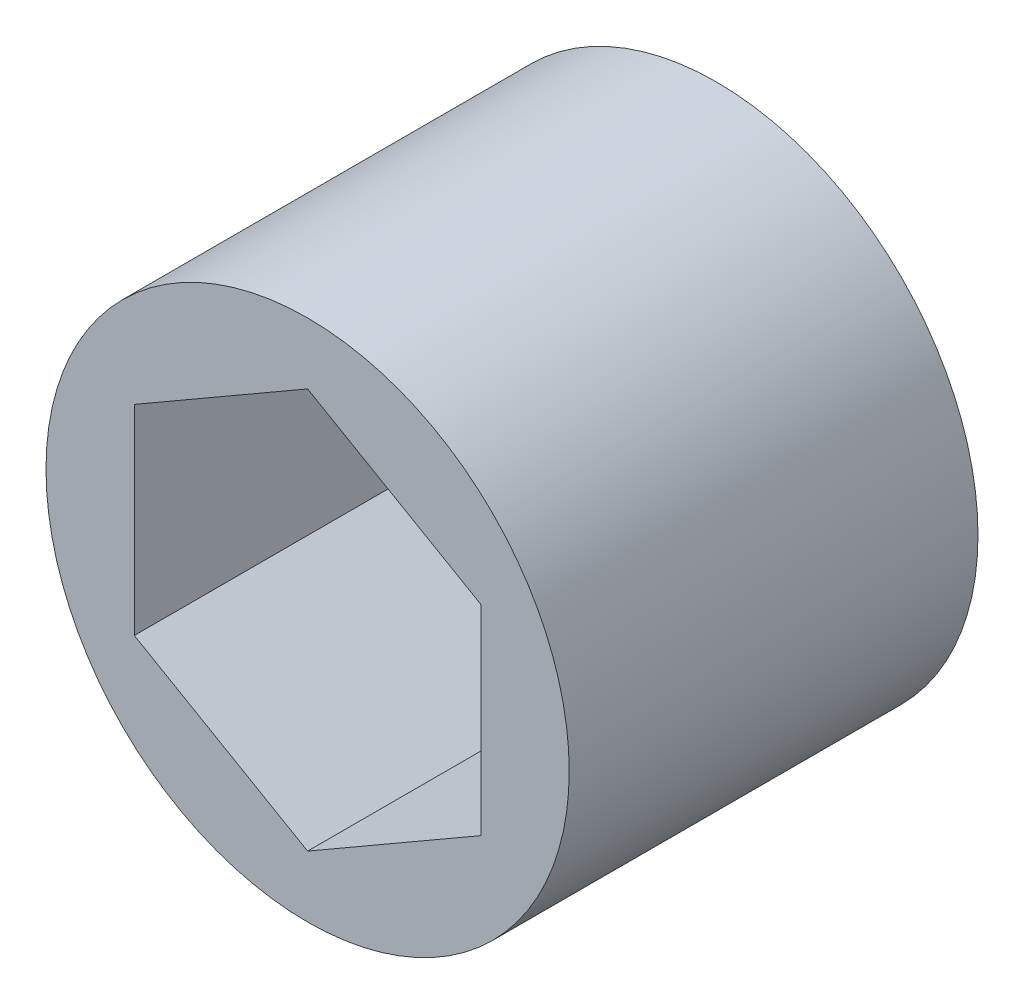
SolidWorks part; units mm, degrees
material "Nylon 101"
ref_plane "Front Plane" through (0, 0, 0) normal (0, 0, 1) x (1, 0, 0)
ref_plane "Top Plane" through (0, 0, 0) normal (0, 1, 0) x (1, 0, 0)
ref_plane "Right Plane" through (0, 0, 0) normal (1, 0, 0) x (0, 0, -1)
sketch "Sketch3" plane through (0, 0, 0) normal (0, 0, 1) x (1, 0, 0)
  line L1 (0, 7.7723) -> (-6.731, 3.8861)
  line L2 (-6.731, 3.8861) -> (-6.731, -3.8861)
  line L3 (-6.731, -3.8861) -> (0, -7.7723)
  line L4 (0, -7.7723) -> (6.731, -3.8861)
  line L5 (6.731, -3.8861) -> (6.731, 3.8861)
  line L6 (6.731, 3.8861) -> (0, 7.7723)
  circle A0 centre (0, 0) radius 10.16
  circle A1 centre (0, 0) radius 6.731 construction
  point P3 (0, 0)
  point P11 (0, 0)
  dimension "D1" = 13.462
  dimension "D2" = 20.32
extrude "Boss-Extrude1" add sketch "Sketch3" along normal mid plane 15.875
